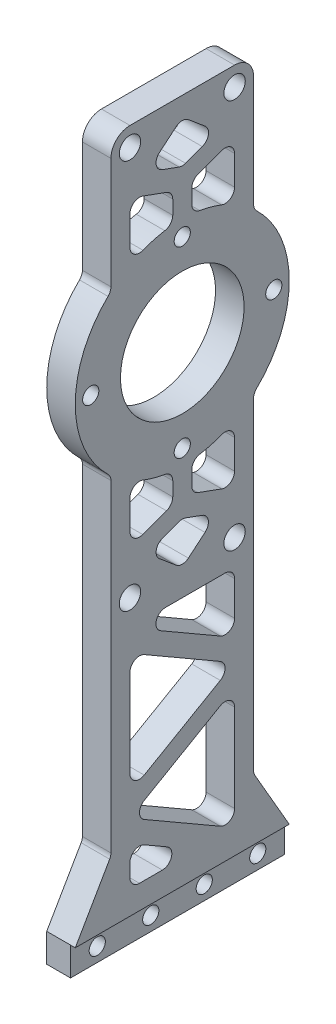
SolidWorks part; units mm, degrees
material "Сплав 2024"
ref_plane "Спереди" through (0, 0, 0) normal (0, 0, 1) x (1, 0, 0)
ref_plane "Сверху" through (0, 0, 0) normal (0, 1, 0) x (1, 0, 0)
ref_plane "Справа" through (0, 0, 0) normal (1, 0, 0) x (0, 0, -1)
sketch "Эскиз1" plane through (0, 0, 0) normal (0, 1, 0) x (1, 0, 0)
  line L1 (0, 0) -> (6, 0)
  line L2 (0, 0) -> (0, -30)
  line L3 (0, -30) -> (6, -30)
  line L4 (6, 0) -> (6, -30)
  dimension "D1" = 6
  dimension "D2" = 30
extrude "Бобышка-Вытянуть1" add sketch "Эскиз1" along normal blind 177
sketch "Эскиз2" plane through (0, 0, 0) normal (-1, 0, 0) x (0, 0, 1)
  line L0 (30, 105) -> (0, 105) construction
  line L3 (15, 177) -> (15, 0) construction
  line L4 (0, 177) -> (30, 177) construction
  line L5 (0, 0) -> (30, 0) construction
  line L6 (30, 0) -> (0, 0) construction
  circle A0 centre (15, 105) radius 22.5
  dimension "D1" = 45
  dimension "D2" = 105
extrude "Бобышка-Вытянуть2" add sketch "Эскиз2" against normal up to surface (6 mm away) up to face at (6, 88.5, 15)
sketch "Эскиз3" plane through (0, 0, 0) normal (-1, 0, 0) x (0, 0, 1)
  circle A0 centre (15, 105) radius 13
  dimension "D1" = 26
extrude "Вырез-Вытянуть1" cut sketch "Эскиз3" against normal through all
sketch "Эскиз4" plane through (6, 0, 0) normal (-1, 0, 0) x (0, 0, 1)
  line L0 (-7.5, 105) -> (37.5, 105) construction
  line L2 (15, 127.5) -> (15, 82.5) construction
  line L3 (30, 105) -> (0, 105) construction
  circle A0 centre (15, 105) radius 19.25 construction
  circle A1 centre (15, 105) radius 22.5 construction
  dimension "D1" = 38.5
  dimension "D2" = 90
hole_wizard "Отверстие с зазором M32" positions "Эскиз6" profile "Эскиз5" hole size "M3" standard "Ansi Metric" end condition up to next
sketch "Эскиз6" plane through (6, -25.0247, 7.2629) normal (-1, 0, 0) x (0, 0, 1)
  line L0 (-14.7629, 130.0247) -> (30.2371, 130.0247) construction
  line L1 (7.7371, 152.5247) -> (7.7371, 107.5247) construction
  circle A0 centre (7.7371, 130.0247) radius 19.25 construction
  point P0 (-11.5129, 130.0247)
  point P6 (7.7371, 110.7747)
  point P10 (26.9871, 130.0247)
  point P12 (7.7371, 149.2747)
sketch "Эскиз5" plane through (6, 105, -4.25) normal (0, 1, 0) x (0, 0, -1)
  line L0 (0, 0) -> (0, 6)
  line L1 (0, 6) -> (1.7, 6)
  line L2 (1.7, 6) -> (1.7, 0)
  line L5 (1.7, 0) -> (0, 0)
  line L11 (0, -6.35) -> (0, 107.95) construction
  dimension "Диаметр сквозного отверстия" = 3.4
  dimension "Глубина сквозного отверстия" = 6
sketch "Эскиз8" plane through (6, 0, 0) normal (1, 0, 0) x (0, 0, -1)
  line L0 (-15, 177) -> (-15, 0) construction
  line L1 (-30, 177) -> (0, 177) construction
  line L2 (-30, 0) -> (0, 0) construction
  line L3 (19.447, 105) -> (-49.447, 105) construction
  line L4 (0, 177) -> (0, 121.7705) construction
  line L5 (-26, 146) -> (-4, 146) construction
  line L6 (-26, 146) -> (-26, 64) construction
  line L7 (-26, 64) -> (-4, 64) construction
  line L8 (-4, 146) -> (-4, 64) construction
  line L9 (-26, 146) -> (-4, 64) construction
  line L11 (-30, 105) -> (0, 105) construction
  point P8 (-15, 105)
  point P9 (-15, 105)
  dimension "D1" = 4
  dimension "D2" = 82
  dimension "D4" = 22
hole_wizard "Отверстие с зазором M41" positions "Эскиз10" profile "Эскиз9" hole size "M4" standard "Ansi Metric" end condition through all
sketch "Эскиз10" plane through (6, 0, 0) normal (1, 0, 0) x (0, 0, -1)
  point P0 (-26, 146)
  point P3 (-4, 146)
  point P6 (-4, 64)
  point P9 (-26, 64)
sketch "Эскиз9" plane through (6, 146, 26) normal (0, 1, 0) x (0, 0, -1)
  line L0 (0, 0) -> (0, 6)
  line L1 (0, 6) -> (2.25, 6)
  line L2 (2.25, 6) -> (2.25, 0)
  line L5 (2.25, 0) -> (0, 0)
  line L11 (0, -6.35) -> (0, 107.95) construction
  dimension "Диаметр сквозного отверстия" = 4.5
  dimension "Глубина сквозного отверстия" = 6
sketch "Эскиз11" plane through (6, 0, 0) normal (1, 0, 0) x (0, 0, -1)
  line L0 (-30, 0) -> (0, 0) construction
  line L1 (-15, 177) -> (-15, 0) construction
  line L2 (-30, 177) -> (0, 177) construction
  line L3 (0, 88.2295) -> (0, 0) construction
  line L4 (-30, 88.2295) -> (-30, 0) construction
  line L5 (-37.5, 3) -> (7.5, 3) construction
  line L6 (-9.375, 6) -> (-9.375, 0) construction
  line L7 (-3.75, 6) -> (-3.75, 0) construction
  line L8 (1.875, 6) -> (1.875, 0) construction
  line L20 (-15, 0) -> (-15, 6) construction
  line L21 (-20.625, 0) -> (-20.625, 6) construction
  line L22 (-26.25, 0) -> (-26.25, 6) construction
  line L23 (-31.875, 0) -> (-31.875, 6) construction
  line L25 (-37.5, 0) -> (7.5, 6) construction
  line L26 (-37.5, 6) -> (7.5, 0) construction
  line L27 (-37.5, 6) -> (7.5, 6) construction
  line L28 (0, 18.9904) -> (7.5, 6)
  line L29 (-30, 18.9904) -> (0, 18.9904)
  line L30 (7.5, 6) -> (7.5, 0)
  line L31 (-37.5, 0) -> (7.5, 0)
  line L32 (-37.5, 6) -> (-37.5, 0)
  line L33 (-37.5, 6) -> (-30, 18.9904)
  point P2 (-15, 3)
  dimension "D1" = 45
  dimension "D2" = 6
  dimension "D3" = 5.625
  dimension "D4" = 5.625
  dimension "D5" = 5.625
  dimension "D6" = 5.625
  dimension "D7" = 120
  dimension "D8" = 5.625
  dimension "D9" = 5.625
  dimension "D10" = 5.625
extrude "Бобышка-Вытянуть3" add sketch "Эскиз11" against normal up to surface (6 mm away) up to face at (0, 146, 23.75)
hole_wizard "Отверстие с зазором M31" positions "Эскиз13" profile "Эскиз12" hole size "M3" standard "Ansi Metric" end condition through all
sketch "Эскиз13" plane through (6, 0, 0) normal (1, 0, 0) x (0, 0, -1)
  line L4 (-31.875, 0) -> (-31.875, 6) construction
  line L8 (1.875, 6) -> (1.875, 0) construction
  line L9 (-9.375, 6) -> (-9.375, 0) construction
  line L10 (-20.625, 0) -> (-20.625, 6) construction
  point P16 (-31.875, 3)
  point P20 (-20.625, 3)
  point P24 (-9.375, 3)
  point P28 (1.875, 3)
sketch "Эскиз12" plane through (6, 3, 31.875) normal (0, 1, 0) x (0, 0, -1)
  line L0 (0, 0) -> (0, 6)
  line L1 (0, 6) -> (1.7, 6)
  line L2 (1.7, 6) -> (1.7, 0)
  line L5 (1.7, 0) -> (0, 0)
  line L11 (0, -6.35) -> (0, 107.95) construction
  dimension "Диаметр сквозного отверстия" = 3.4
  dimension "Глубина сквозного отверстия" = 6
sketch "Эскиз14" plane through (6, 0, 0) normal (1, 0, 0) x (0, 0, -1)
  line L5 (-37.5, 0) -> (7.5, 0)
  line L6 (-37.5, 0) -> (-37.5, 6)
  line L7 (-37.5, 6) -> (7.5, 6)
  line L8 (7.5, 0) -> (7.5, 6)
extrude "Вырез-Вытянуть2" cut sketch "Эскиз14" against normal blind 1
sketch "Эскиз15" plane through (6, 0, 0) normal (1, 0, 0) x (0, 0, -1)
  line L0 (0, 177) -> (0, 121.7705) construction
  line L1 (-30, 177) -> (0, 177)
  line L2 (-30, 177) -> (-30, 150.0245)
  line L3 (-30, 150.0245) -> (0, 150.0245)
  line L4 (0, 177) -> (0, 150.0245)
  circle A0 centre (-26, 146) radius 2.25 construction
  dimension "D1" = 4.0245
extrude "Вырез-Вытянуть3" cut sketch "Эскиз15" against normal up to surface (6 mm away) up to face at (0, 3, 30.175)
fillet "Скругление1" radius 4 2 edges at (3, 150.0245, 30) (3, 150.0245, 0)
sketch "Эскиз16" plane through (0, 0, 0) normal (-1, 0, 0) x (0, 0, 1)
  line L0 (4, 0) -> (4, 150.0245) construction
  line L1 (-7.5, 0) -> (37.5, 0) construction
  line L2 (4, 150.0245) -> (26, 150.0245) construction
  line L3 (26, 0) -> (26, 150.0245) construction
  line L4 (0, 88.2295) -> (0, 18.9904) construction
  line L5 (30, 88.2295) -> (30, 18.9904) construction
  line L6 (15, 177) -> (15, 0) construction
  line L7 (0, 146.0245) -> (30, 146.0245) construction
  line L8 (0, 146.0245) -> (0, 121.7705) construction
  line L9 (30, 146.0245) -> (30, 121.7705) construction
  line L10 (15, 146.0245) -> (4, 136.7944) construction
  line L11 (15, 146.0245) -> (26, 136.7944) construction
  line L12 (0, 136.7944) -> (30, 136.7944) construction
  line L13 (4, 136.7944) -> (4, 124.6278)
  line L14 (26, 136.7944) -> (26, 124.6278)
  line L15 (13, 133.5187) -> (13, 127.4109)
  line L16 (17, 133.5187) -> (17, 127.4109)
  line L17 (4, 136.7944) -> (13, 133.5187)
  line L18 (0, 133.5187) -> (30, 133.5187) construction
  line L19 (26, 136.7944) -> (17, 133.5187)
  line L20 (7.5382, 139.7634) -> (15, 137.0475)
  line L21 (22.4618, 139.7634) -> (15, 137.0475)
  line L22 (7.5382, 139.7634) -> (15, 146.0245)
  line L23 (15, 146.0245) -> (22.4618, 139.7634)
  line L24 (15, 105) -> (22.4618, 105) construction
  line L25 (13, 76.4791) -> (13, 82.5891)
  line L26 (17, 76.4791) -> (17, 82.5891)
  line L27 (26, 73.2033) -> (17, 76.4791)
  line L28 (26, 73.2033) -> (26, 85.3722)
  line L29 (4, 73.2033) -> (4, 85.3722)
  line L30 (4, 73.2033) -> (13, 76.4791)
  line L31 (7.5605, 70.2425) -> (15, 72.9503)
  line L32 (22.4395, 70.2425) -> (15, 72.9503)
  line L33 (15, 64) -> (22.4395, 70.2425)
  line L34 (7.5605, 70.2425) -> (15, 64)
  line L35 (26, 53.8812) -> (26, 28.4778)
  line L36 (26, 28.4778) -> (4, 41.1795)
  line L37 (4, 41.1795) -> (26, 53.8812)
  line L38 (4, 58.5) -> (26, 58.5)
  line L39 (26, 58.5) -> (4, 45.7983)
  line L40 (4, 45.7983) -> (4, 58.5)
  line L41 (4, 36.5607) -> (26, 23.859)
  line L42 (26, 23.859) -> (4, 11.1573)
  line L43 (4, 11.1573) -> (4, 36.5607)
  line L44 (11.7276, 11) -> (26, 19.2402)
  line L45 (26, 19.2402) -> (26, 11)
  line L46 (26, 11) -> (11.7276, 11)
  line L47 (34.6132, 11) -> (-4.6132, 11) construction
  line L48 (30, 18.9904) -> (37.5, 6) construction
  line L49 (-7.5, 6) -> (0, 18.9904) construction
  line L50 (-7.5, 6) -> (37.5, 6) construction
  line L51 (0, 76.4791) -> (30, 76.4791) construction
  line L52 (0, 73.2033) -> (30, 73.2033) construction
  line L53 (0, 70.2425) -> (30, 70.2425) construction
  line L54 (26, 64) -> (4, 64) construction
  circle A0 centre (15, 105) radius 22.5 construction
  arc A1 (4, 124.6278) -> (13, 127.4109) centre (15, 105) cw
  arc A2 (17, 127.4109) -> (26, 124.6278) centre (15, 105) cw
  arc A3 (17, 82.5891) -> (26, 85.3722) centre (15, 105) ccw
  arc A4 (4, 85.3722) -> (13, 82.5891) centre (15, 105) ccw
  circle A5 centre (4, 64) radius 2.25 construction
  point P12 (4, 124.6278)
  point P13 (26, 124.6278)
  point P20 (15, 146.0245)
  dimension "D3" = 4
  dimension "D16" = 5.5
  dimension "D1" = 4
  dimension "D2" = 4
  dimension "D4" = 100
  dimension "D5" = 4
  dimension "D6" = 2
  dimension "D7" = 4
  dimension "D8" = 110
  dimension "D9" = 30
  dimension "D10" = 4
  dimension "D11" = 4
  dimension "D12" = 4
  dimension "D13" = 60
  dimension "D14" = 60
  dimension "D15" = 5
  dimension "D17" = 6.11
  dimension "D18" = 4
  dimension "D19" = 2
  dimension "D20" = 110
  dimension "D21" = 4
  dimension "D22" = 100
extrude "Вырез-Вытянуть4" cut sketch "Эскиз16" against normal through all
fillet "Скругление3" radius 2 42 edges at (3, 127.4109, 13) (3, 124.6278, 26) (3, 124.6278, 4) (3, 127.4109, 17) (3, 133.5187, 17) (3, 136.7944, 4) (3, 133.5187, 13) (3, 136.7944, 26) (3, 137.0475, 15) (3, 139.7634, 22.4618) (3, 139.7634, 7.5382) (3, 146.0245, 15) (3, 70.2425, 7.5605) (3, 70.2425, 22.4395) (3, 85.3722, 4) (3, 76.4791, 17) (3, 82.5891, 17) (3, 73.2033, 4) (3, 64, 15) (3, 72.9503, 15) (3, 82.5891, 13) (3, 85.3722, 26) (3, 76.4791, 13) (3, 73.2033, 26) (3, 11, 11.7276) (3, 11, 26) (3, 11.1573, 4) (3, 19.2402, 26) (3, 23.859, 26) (3, 28.4778, 26) (3, 36.5607, 4) (3, 53.8812, 26) (3, 41.1795, 4) (3, 45.7983, 4) (3, 58.5, 4) (3, 58.5, 26) (3, 18.9904, 30) (3, 18.9904, 0) (3, 121.7705, 0) (3, 121.7705, 30) (3, 88.2295, 30) (3, 88.2295, 0)
equation "\"D4@Эскиз11\"=\"D3@Эскиз11\""
equation "\"D5@Эскиз11\"=\"D3@Эскиз11\""
equation "\"D6@Эскиз11\"=\"D4@Эскиз11\""
equation "\"D3@Эскиз11\"=\"D1@Эскиз11\" / 8"
equation "\"D13@Эскиз16\"=\"D9@Эскиз16\"*2"
equation "\"D11@Эскиз16\"=\"D10@Эскиз16\""
equation "\"D12@Эскиз16\"=\"D10@Эскиз16\""
equation "\"D8@Эскиз11\"=\"D3@Эскиз11\""
equation "\"D9@Эскиз11\"=\"D3@Эскиз11\""
equation "\"D10@Эскиз11\"=\"D3@Эскиз11\""
